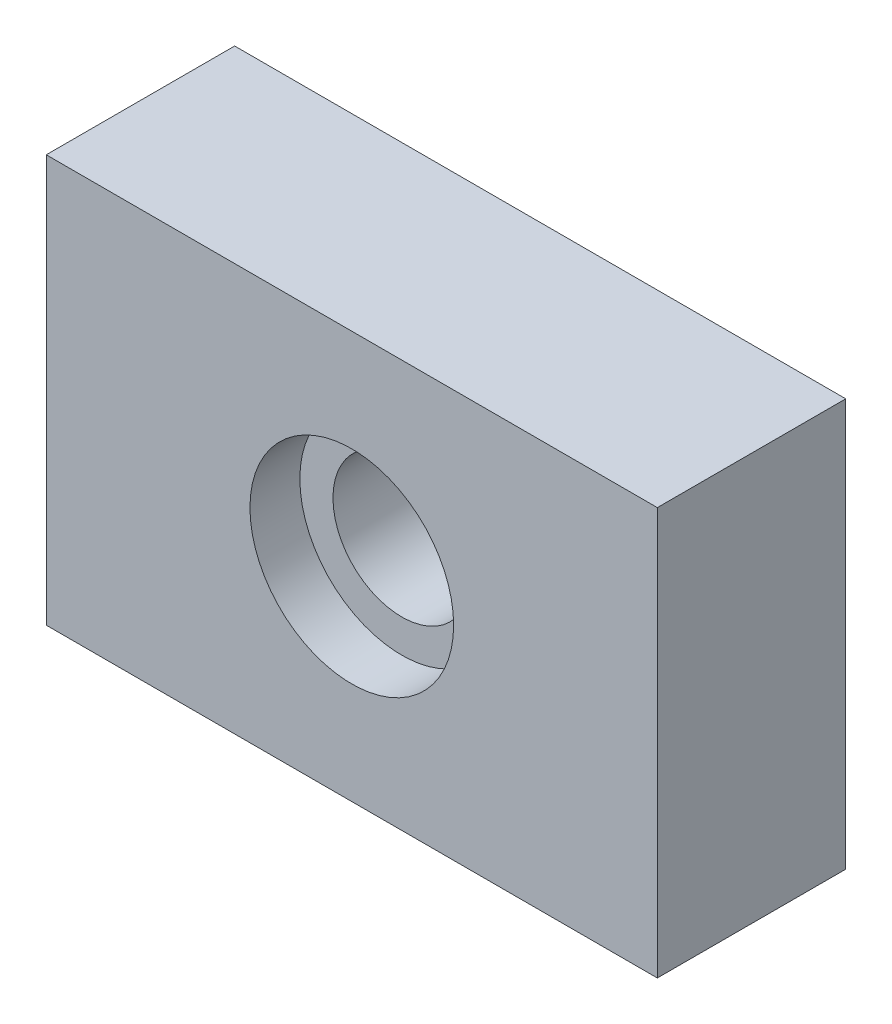
SolidWorks part; units mm, degrees
material "1060 Alloy"
ref_plane "Front Plane" through (0, 0, 0) normal (0, 0, 1) x (1, 0, 0)
ref_plane "Top Plane" through (0, 0, 0) normal (0, 1, 0) x (1, 0, 0)
ref_plane "Right Plane" through (0, 0, 0) normal (1, 0, 0) x (0, 0, -1)
sketch "Sketch1" plane through (0, 0, 0) normal (0, 0, 1) x (1, 0, 0)
  line L1 (0, 0) -> (152.4, 0)
  line L2 (0, 0) -> (0, 101.6)
  line L3 (0, 101.6) -> (152.4, 101.6)
  line L4 (152.4, 0) -> (152.4, 101.6)
  dimension "D1" = 152.4
  dimension "D2" = 101.6
extrude "Boss-Extrude1" add sketch "Sketch1" along normal blind 46.99
sketch "Sketch2" plane through (0, 0, 0) normal (0, 0, -1) x (-1, 0, 0)
  line L0 (0, 50.8) -> (-152.4, 50.8) construction
  line L1 (0, 101.6) -> (0, 0) construction
  line L2 (-152.4, 0) -> (-152.4, 101.6) construction
  line L4 (-152.4, 101.6) -> (0, 101.6) construction
  line L5 (-76.2, 101.6) -> (-76.2, 0) construction
  line L6 (0, 0) -> (-152.4, 0) construction
  circle A0 centre (-76.2, 50.8) radius 25.4
  circle A1 centre (-76.2, 50.8) radius 17.145
  dimension "D1" = 50.8
  dimension "D2" = 34.29
extrude "Cut-Extrude1" cut sketch "Sketch2" against normal through all contours A1
extrude "Cut-Extrude3" cut sketch "Sketch2<2>" against normal blind 12.446
sketch "Sketch2<2>" plane through (0, 0, 0) normal (0, 0, -1) x (-1, 0, 0) same geometry as "Sketch2"
ref_plane "Plane2" through (0, 0, 23.495) normal (0, 0, -1) x (-1, 0, 0)
mirror "Mirror2" about plane through (0, 0, 23.495) normal (0, 0, -1) of "Cut-Extrude3"
hole_wizard "Tap Drill for 1/2-13 Tap1" positions "Sketch4" profile "Sketch5" hole size "1/2-13" standard "ANSI Inch"
sketch "Sketch4" plane through (0, 0, 0) normal (0, -1, 0) x (-1, 0, 0)
  line L0 (55.88, -23.495) -> (-55.88, -23.495) construction
  line L2 (-76.2, -46.99) -> (-76.2, 0) construction
  line L3 (0, -46.99) -> (-152.4, -46.99) construction
  line L4 (0, 0) -> (-152.4, 0) construction
  point P0 (-66.6533, -23.495)
  point P4 (-28.5533, -23.495)
  dimension "D1" = 47.6467
  dimension "D2" = 38.1
sketch "Sketch5" plane through (66.6533, 0, 23.495) normal (1, 0, 0) x (0, 0, -1)
  line L0 (0, 0) -> (0, 22.2695)
  line L1 (0, 22.2695) -> (5.3581, 19.05)
  line L2 (5.3581, 19.05) -> (5.3581, 0)
  line L5 (5.3581, 0) -> (0, 0)
  line L10 (0, 22.2695) -> (-5.3581, 19.05) construction
  line L11 (0, -6.35) -> (0, 107.95) construction
  dimension "Hole Dia." = 10.7163
  dimension "Hole Depth" = 19.05
  dimension "Drill Angle" = 118
equation "\"through_diamiter\"= 1.35"
equation "\"D2@Sketch2\"= \"through_diamiter\""
equation "\"bearing depth\"= 0.5"
equation "\"hole spacing\"= 0.75"
equation "\"D1@Sketch4\" = \"hole spacing\"+\"center_distance\""
equation "\"center_distance\"= 1.125855"
